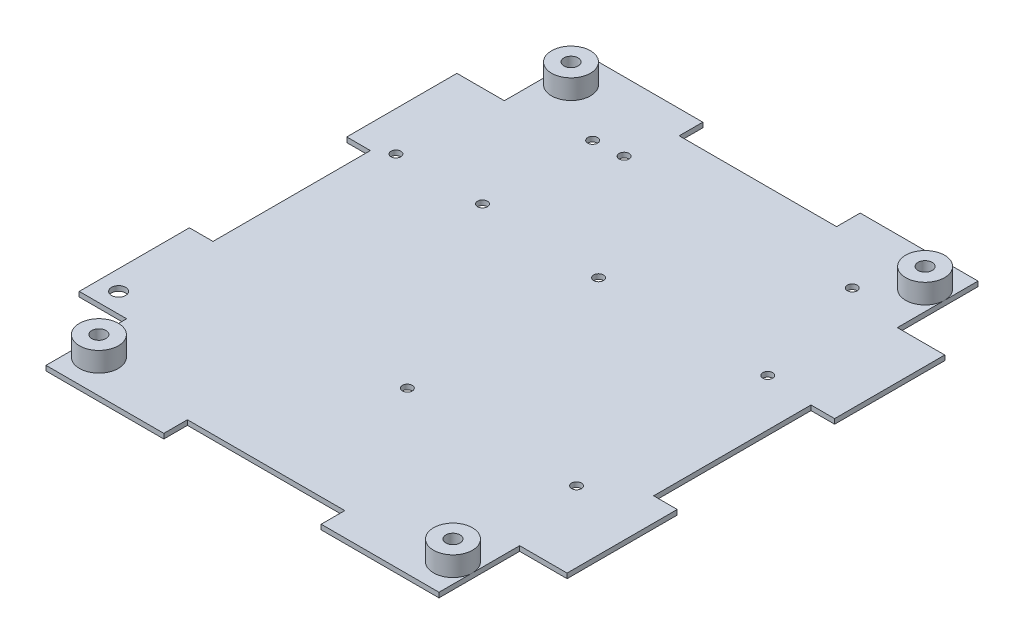
SolidWorks part; units mm, degrees
ref_plane "Front Plane" through (0, 0, 0) normal (0, 0, 1) x (1, 0, 0)
ref_plane "Top Plane" through (0, 0, 0) normal (0, 1, 0) x (1, 0, 0)
ref_plane "Right Plane" through (0, 0, 0) normal (1, 0, 0) x (0, 0, -1)
sketch "Sketch1" plane through (0, 0, 0) normal (0, 1, 0) x (1, 0, 0)
  line L0 (-25.4, 86.995) -> (-63.4314, 86.995)
  line L1 (-88.9, -101.6) -> (88.9, -101.6) construction
  line L2 (101.6, -88.9) -> (101.6, 88.9) construction
  line L3 (88.9, 101.6) -> (-88.9, 101.6) construction
  line L4 (-78.74, -60.96) -> (-63.4314, -60.96)
  line L5 (-63.4314, -60.96) -> (-63.4314, -86.995)
  line L6 (-63.4314, -86.995) -> (-25.4, -86.995)
  line L7 (63.4314, -86.995) -> (63.4314, -60.96)
  line L8 (63.4314, -60.96) -> (78.74, -60.96)
  line L9 (78.74, -60.96) -> (78.74, -25.4)
  line L10 (78.74, 60.96) -> (63.4314, 60.96)
  line L11 (63.4314, 60.96) -> (63.4314, 86.995)
  line L12 (63.4314, 86.995) -> (25.4, 86.995)
  line L13 (-63.4314, 86.995) -> (-63.4314, 60.96)
  line L14 (-63.4314, 60.96) -> (-78.74, 60.96)
  line L15 (-78.74, 60.96) -> (-78.74, 25.4)
  line L16 (-78.74, -25.4) -> (-78.74, -60.96)
  line L17 (-78.74, -25.4) -> (-71.12, -25.4)
  line L19 (-78.74, 25.4) -> (-71.12, 25.4)
  line L20 (-71.12, -25.4) -> (-71.12, 25.4)
  line L22 (-25.4, 86.995) -> (-25.4, 79.375)
  line L23 (-25.4, 79.375) -> (25.4, 79.375)
  line L24 (25.4, 86.995) -> (25.4, 79.375)
  line L25 (78.74, 25.4) -> (71.12, 25.4)
  line L27 (78.74, -25.4) -> (71.12, -25.4)
  line L28 (71.12, 25.4) -> (71.12, -25.4)
  line L30 (25.4, -86.995) -> (25.4, -79.375)
  line L31 (25.4, -79.375) -> (-25.4, -79.375)
  line L32 (-25.4, -86.995) -> (-25.4, -79.375)
  line L33 (78.74, 25.4) -> (78.74, 60.96)
  line L34 (25.4, -86.995) -> (63.4314, -86.995)
  line L35 (-101.6, 88.9) -> (-101.6, -88.9) construction
  arc A0 (88.9, -101.6) -> (101.6, -88.9) centre (88.9, -88.9) ccw construction
  arc A1 (-101.6, -88.9) -> (-88.9, -101.6) centre (-88.9, -88.9) ccw construction
  arc A2 (101.6, 88.9) -> (88.9, 101.6) centre (88.9, 88.9) ccw construction
  arc A3 (-101.6, 88.9) -> (-88.9, 101.6) centre (-88.9, 88.9) cw construction
  circle A4 centre (-57.15, 76.2) radius 2.286
  circle A5 centre (57.15, 76.2) radius 2.286
  circle A6 centre (57.15, -76.2) radius 2.286
  circle A7 centre (-57.15, -76.2) radius 2.286
  point P3 (0, 101.6)
  point P5 (101.6, 0)
  point P13 (101.6, 101.6)
  point P16 (-101.6, 101.6)
  point P38 (-71.12, 0)
  point P55 (0, -79.375)
  point P56 (0, 79.375)
  point P57 (71.12, 0)
  dimension "D2" = 12.7
  dimension "D11" = 4.572
  dimension "D8" = 44.45
  dimension "D1" = 203.2
  dimension "D3" = 203.2
  dimension "D4" = 22.86
  dimension "D5" = 15.3086
  dimension "D6" = 35.56
  dimension "D7" = 173.99
  dimension "D12" = 50.8
  dimension "D13" = 25.4
  dimension "D14" = 44.45
  dimension "D15" = 25.4
  dimension "D18" = 7.62
extrude "Main Body" add sketch "Sketch1" along normal blind 1.5875
sketch "Sketch5" plane through (0, 1.5875, 0) normal (0, 1, 0) x (1, 0, 0)
  line L0 (55.88, 26.67) -> (1.27, 26.67)
  line L1 (48.895, 90.17) -> (-32.385, 90.17)
  line L2 (48.895, 90.17) -> (48.895, 39.37)
  line L3 (48.895, 39.37) -> (-32.385, 39.37)
  line L4 (-32.385, 90.17) -> (-32.385, 39.37)
  line L5 (48.895, 90.17) -> (-32.385, 39.37) construction
  line L6 (48.895, 39.37) -> (-32.385, 90.17) construction
  line L7 (45.085, 64.77) -> (-28.575, 64.77)
  line L8 (-60.96, -54.61) -> (-15.24, -54.61)
  line L9 (-60.96, -54.61) -> (-60.96, 11.43)
  line L10 (-60.96, 11.43) -> (-15.24, 11.43)
  line L11 (-15.24, -54.61) -> (-15.24, 11.43)
  line L13 (-35.56, 26.035) -> (-68.58, 26.035)
  line L14 (-35.56, 26.035) -> (-35.56, 66.675)
  line L15 (-35.56, 66.675) -> (-68.58, 66.675)
  line L16 (-68.58, 26.035) -> (-68.58, 66.675)
  line L17 (-35.56, 26.035) -> (-68.58, 66.675) construction
  line L18 (-35.56, 66.675) -> (-68.58, 26.035) construction
  line L19 (-38.1, 28.575) -> (-66.04, 28.575)
  line L20 (-38.1, 28.575) -> (-38.1, 64.135)
  line L21 (-38.1, 64.135) -> (-66.04, 64.135)
  line L22 (-66.04, 28.575) -> (-66.04, 64.135)
  line L23 (-38.1, 28.575) -> (-66.04, 64.135) construction
  line L24 (-38.1, 64.135) -> (-66.04, 28.575) construction
  line L36 (25.4, 86.995) -> (25.4, 79.375)
  line L38 (25.4, 79.375) -> (-25.4, 79.375)
  line L40 (71.12, 25.4) -> (78.74, 25.4)
  line L41 (78.74, 25.4) -> (78.74, 60.96)
  line L42 (78.74, 60.96) -> (63.4314, 60.96)
  line L43 (63.4314, 60.96) -> (63.4314, 86.995)
  line L44 (63.4314, 86.995) -> (25.4, 86.995)
  line L45 (25.4, 79.375) -> (-25.4, 79.375)
  line L49 (-63.4314, 86.995) -> (-63.4314, 60.96)
  line L50 (-63.4314, 60.96) -> (-78.74, 60.96)
  line L51 (-78.74, 60.96) -> (-78.74, 25.4)
  line L52 (-78.74, 25.4) -> (-71.12, 25.4)
  line L53 (-71.12, 25.4) -> (-71.12, -25.4)
  line L54 (-71.12, -25.4) -> (-78.74, -25.4)
  line L55 (-78.74, -25.4) -> (-78.74, -60.96)
  line L56 (-78.74, -60.96) -> (-63.4314, -60.96)
  line L57 (-63.4314, -60.96) -> (-63.4314, -86.995)
  line L58 (-63.4314, -86.995) -> (-25.4, -86.995)
  line L61 (71.12, -25.4) -> (71.12, 25.4)
  line L62 (71.12, -25.4) -> (71.12, 25.4)
  line L63 (63.4314, -86.995) -> (63.4314, -60.96)
  line L64 (63.4314, -60.96) -> (78.74, -60.96)
  line L65 (78.74, -60.96) -> (78.74, -25.4)
  line L66 (78.74, -25.4) -> (71.12, -25.4)
  line L74 (71.12, 25.4) -> (78.74, 25.4)
  line L75 (78.74, 25.4) -> (78.74, 60.96)
  line L76 (78.74, 60.96) -> (63.4314, 60.96)
  line L77 (63.4314, 60.96) -> (63.4314, 86.995)
  line L78 (63.4314, 86.995) -> (25.4, 86.995)
  line L83 (-63.4314, 86.995) -> (-63.4314, 60.96)
  line L84 (-63.4314, 60.96) -> (-78.74, 60.96)
  line L85 (-78.74, 60.96) -> (-78.74, 25.4)
  line L86 (-78.74, 25.4) -> (-71.12, 25.4)
  line L87 (-71.12, 25.4) -> (-71.12, -25.4)
  line L88 (-71.12, -25.4) -> (-78.74, -25.4)
  line L89 (-78.74, -25.4) -> (-78.74, -60.96)
  line L90 (-78.74, -60.96) -> (-63.4314, -60.96)
  line L91 (-63.4314, -60.96) -> (-63.4314, -86.995)
  line L92 (-63.4314, -86.995) -> (-25.4, -86.995)
  line L97 (63.4314, -86.995) -> (63.4314, -60.96)
  line L98 (63.4314, -60.96) -> (78.74, -60.96)
  line L99 (78.74, -60.96) -> (78.74, -25.4)
  line L100 (78.74, -25.4) -> (71.12, -25.4)
  line L107 (-25.4, 86.995) -> (-63.4314, 86.995)
  line L109 (-25.4, 86.995) -> (-63.4314, 86.995)
  line L110 (-25.4, -86.995) -> (-25.4, -79.375)
  line L111 (-25.4, -86.995) -> (-25.4, -79.375)
  line L112 (-25.4, -79.375) -> (25.4, -79.375)
  line L113 (-25.4, -79.375) -> (25.4, -79.375)
  line L114 (25.4, -79.375) -> (25.4, -86.995)
  line L115 (25.4, -79.375) -> (25.4, -86.995)
  line L116 (25.4, -86.995) -> (63.4314, -86.995)
  line L117 (25.4, -86.995) -> (63.4314, -86.995)
  line L122 (25.4, 86.995) -> (25.4, 79.375)
  line L126 (-25.4, 79.375) -> (-25.4, 86.995)
  line L127 (-25.4, 79.375) -> (-25.4, 86.995)
  circle A0 centre (1.27, 26.67) radius 1.5875
  circle A1 centre (55.88, 26.67) radius 1.5875
  circle A2 centre (55.88, -35.052) radius 1.5875
  circle A3 centre (1.27, -35.052) radius 1.5875
  circle A4 centre (-15.24, -54.61) radius 1.27
  circle A5 centre (-60.96, -54.61) radius 1.27
  circle A6 centre (-60.96, 11.43) radius 1.27
  circle A7 centre (-15.24, 11.43) radius 1.27
  circle A8 centre (-28.575, 64.77) radius 1.5875
  circle A9 centre (45.085, 64.77) radius 1.5875
  circle A10 centre (-66.04, 28.575) radius 1.5875
  circle A11 centre (-66.04, 64.135) radius 1.5875
  circle A12 centre (-38.1, 64.135) radius 1.5875
  circle A13 centre (-38.1, 28.575) radius 1.5875
  circle A14 centre (57.15, 76.2) radius 2.286 construction
  circle A15 centre (-57.15, 76.2) radius 2.286 construction
  circle A16 centre (57.15, 76.2) radius 2.286
  circle A17 centre (-57.15, 76.2) radius 2.286
  circle A18 centre (57.15, 76.2) radius 6.2814
  circle A19 centre (-57.15, 76.2) radius 6.2814
  circle A20 centre (-72.39, -54.61) radius 2.286
  text T0 "<b>LIPO</b>"
  point P0 (8.255, 64.77)
  point P2 (55.88, -35.052)
  point P4 (1.27, -35.052)
  point P6 (1.27, 26.67)
  point P8 (55.88, 26.67)
  point P25 (28.575, 26.67)
  point P40 (-15.24, -21.59)
  point P42 (-38.1, 11.43)
  point P44 (-38.1, -21.59)
  point P52 (-52.07, 46.355)
  point P57 (-52.07, 46.355)
  point P58 (8.255, 64.77)
  point P78 (-52.07, 66.675)
  point P81 (0, 0)
  point P85 (-85.1291, -58.5739)
  dimension "D8" = 3.175
  dimension "D9" = 3.175
  dimension "D10" = 3.175
  dimension "D11" = 3.175
  dimension "D17" = 2.54
  dimension "D20" = 3.175
  dimension "D27" = 3.175
  dimension "D30" = 4.572
  dimension "D2" = 54.61
  dimension "D3" = 12.7
  dimension "D4" = 81.28
  dimension "D5" = 61.722
  dimension "D6" = 50.8
  dimension "D7" = 22.225
  dimension "D12" = 21.59
  dimension "D13" = 28.575
  dimension "D14" = 28.575
  dimension "D15" = 45.72
  dimension "D16" = 66.04
  dimension "D18" = 21.59
  dimension "D19" = 38.1
  dimension "D21" = 73.66
  dimension "D22" = 3.175
  dimension "D23" = 40.64
  dimension "D24" = 33.02
  dimension "D25" = 35.56
  dimension "D26" = 27.94
  dimension "D28" = 3.175
  dimension "D29" = 9.525
  dimension "D31" = 6.35
  dimension "D32" = 6.35
  dimension "D1" = 0
sketch "Sketch13" plane through (0, 1.5875, 0) normal (0, 1, 0) x (1, 0, 0)
  line L32 (25.4, 79.375) -> (-25.4, 79.375)
  line L33 (25.4, 86.995) -> (25.4, 79.375)
  line L36 (63.4314, 86.995) -> (25.4, 86.995)
  line L37 (-63.4314, 86.995) -> (-63.4314, 60.96)
  line L38 (-63.4314, 60.96) -> (-78.74, 60.96)
  line L39 (-78.74, 60.96) -> (-78.74, 25.4)
  line L40 (-78.74, 25.4) -> (-71.12, 25.4)
  line L41 (-71.12, 25.4) -> (-71.12, -25.4)
  line L42 (-71.12, -25.4) -> (-78.74, -25.4)
  line L43 (-78.74, -25.4) -> (-78.74, -60.96)
  line L44 (-78.74, -60.96) -> (-63.4314, -60.96)
  line L45 (-63.4314, -60.96) -> (-63.4314, -86.995)
  line L46 (-63.4314, -86.995) -> (-25.4, -86.995)
  line L47 (-25.4, -86.995) -> (-25.4, -79.375)
  line L48 (-25.4, -79.375) -> (25.4, -79.375)
  line L49 (25.4, -79.375) -> (25.4, -86.995)
  line L50 (25.4, -86.995) -> (63.4314, -86.995)
  line L51 (63.4314, -86.995) -> (63.4314, -60.96)
  line L52 (63.4314, -60.96) -> (78.74, -60.96)
  line L53 (78.74, -60.96) -> (78.74, -25.4)
  line L54 (78.74, -25.4) -> (71.12, -25.4)
  line L55 (71.12, -25.4) -> (71.12, 25.4)
  line L56 (71.12, 25.4) -> (78.74, 25.4)
  line L57 (78.74, 25.4) -> (78.74, 60.96)
  line L58 (78.74, 60.96) -> (63.4314, 60.96)
  line L59 (63.4314, 60.96) -> (63.4314, 86.995)
  line L60 (-25.4, 86.995) -> (-63.4314, 86.995)
  line L61 (25.4, 86.995) -> (25.4, 79.375)
  line L64 (25.4, 79.375) -> (-25.4, 79.375)
  line L68 (63.4314, 86.995) -> (25.4, 86.995)
  line L69 (-63.4314, 86.995) -> (-63.4314, 60.96)
  line L70 (-63.4314, 60.96) -> (-78.74, 60.96)
  line L71 (-78.74, 60.96) -> (-78.74, 25.4)
  line L72 (-78.74, 25.4) -> (-71.12, 25.4)
  line L73 (-71.12, 25.4) -> (-71.12, -25.4)
  line L74 (-71.12, -25.4) -> (-78.74, -25.4)
  line L75 (-78.74, -25.4) -> (-78.74, -60.96)
  line L76 (-78.74, -60.96) -> (-63.4314, -60.96)
  line L77 (-63.4314, -60.96) -> (-63.4314, -86.995)
  line L78 (-63.4314, -86.995) -> (-25.4, -86.995)
  line L79 (-25.4, -86.995) -> (-25.4, -79.375)
  line L80 (-25.4, -79.375) -> (25.4, -79.375)
  line L81 (25.4, -79.375) -> (25.4, -86.995)
  line L82 (25.4, -86.995) -> (63.4314, -86.995)
  line L83 (63.4314, -86.995) -> (63.4314, -60.96)
  line L84 (63.4314, -60.96) -> (78.74, -60.96)
  line L85 (78.74, -60.96) -> (78.74, -25.4)
  line L86 (78.74, -25.4) -> (71.12, -25.4)
  line L87 (71.12, -25.4) -> (71.12, 25.4)
  line L88 (71.12, 25.4) -> (78.74, 25.4)
  line L89 (78.74, 25.4) -> (78.74, 60.96)
  line L90 (78.74, 60.96) -> (63.4314, 60.96)
  line L91 (63.4314, 60.96) -> (63.4314, 86.995)
  line L104 (-25.4, 79.375) -> (-25.4, 86.995)
  line L105 (-25.4, 79.375) -> (-25.4, 86.995)
  line L108 (-25.4, 86.995) -> (-63.4314, 86.995)
  circle A0 centre (57.15, 76.2) radius 2.286 construction
  circle A1 centre (-57.15, 76.2) radius 2.286 construction
  circle A2 centre (-57.15, -76.2) radius 2.286 construction
  circle A3 centre (57.15, -76.2) radius 2.286 construction
  circle A4 centre (57.15, 76.2) radius 2.286
  circle A5 centre (-57.15, 76.2) radius 2.286
  circle A6 centre (-57.15, -76.2) radius 2.286
  circle A7 centre (57.15, -76.2) radius 2.286
  circle A8 centre (57.15, 76.2) radius 6.2814
  circle A9 centre (-57.15, -76.2) radius 6.2814
  circle A10 centre (-57.15, 76.2) radius 6.2814
  circle A11 centre (57.15, -76.2) radius 6.2814
  point P40 (-57.15, -76.2)
  point P46 (57.15, 76.2)
  point P52 (57.15, -76.2)
  point P58 (-57.15, 76.2)
  circle M45 centre (57.15, -76.2) radius 2.286
  circle M46 centre (-57.15, 76.2) radius 2.286
  circle M47 centre (57.15, 76.2) radius 2.286
  circle M48 centre (-57.15, -76.2) radius 2.286
  dimension "D1" = 0
extrude "Boss-Extrude9" add sketch "Sketch13" along normal blind 6.35 contours A11 M45 | A11 M45 | A9 M48 | A9 M48 | A10 M46 | A10 M46 | A8 M47 | A8 M47 region at (-57.15, 1.5875, -82.3038) region at (-57.15, 1.5875, 70.0962) region at (51.0462, 1.5875, 76.2) region at (51.0462, 1.5875, -76.2)
extrude "Cut-Extrude3" cut sketch "Sketch5" against normal up to next contours A2 | A3 | A0 | A1 | A13 | A10 | A12 | A8 | A9 | A20
